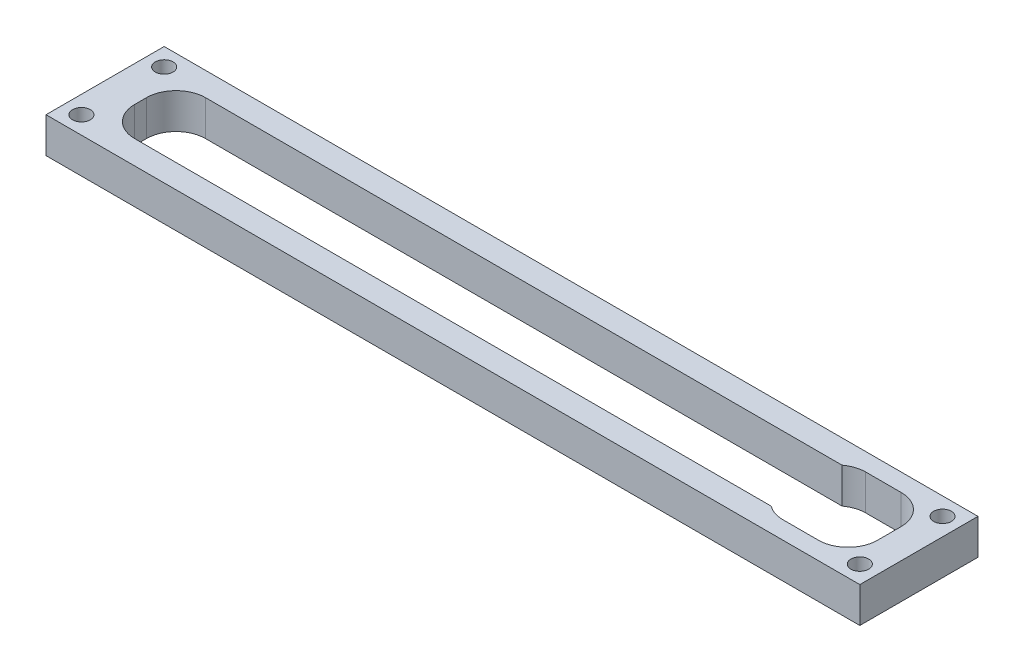
SolidWorks part; units mm, degrees
ref_plane "Front Plane" through (0, 0, 0) normal (0, 0, 1) x (1, 0, 0)
ref_plane "Top Plane" through (0, 0, 0) normal (0, 1, 0) x (1, 0, 0)
ref_plane "Right Plane" through (0, 0, 0) normal (1, 0, 0) x (0, 0, -1)
sketch "Sketch1" plane through (0, 0, 0) normal (0, 1, 0) x (1, 0, 0)
  line L0 (68.8639, 20) -> (68.8639, 0) construction
  line L1 (0, 0) -> (137.7278, 0)
  line L2 (0, 0) -> (0, 20)
  line L3 (0, 20) -> (137.7278, 20)
  line L4 (137.7278, 0) -> (137.7278, 20)
  line L5 (0, 10) -> (137.7278, 10) construction
  line L6 (68.8639, 16) -> (68.8639, 4) construction
  line L7 (6, 16) -> (131.7278, 16)
  line L8 (6, 16) -> (6, 4)
  line L9 (6, 4) -> (131.7278, 4)
  line L10 (131.7278, 16) -> (131.7278, 4)
  line L11 (6, 10) -> (131.7278, 10) construction
  circle A0 centre (3, 17) radius 1.5
  circle A1 centre (3, 3) radius 1.5
  circle A2 centre (134.7278, 3) radius 1.5
  circle A3 centre (134.7278, 17) radius 1.5
  point P17 (68.8639, 10)
  point P18 (68.8639, 10)
  dimension "D7" = 3
  dimension "D1" = 137.7278
  dimension "D2" = 20
  dimension "D3" = 125.7278
  dimension "D4" = 12
  dimension "D5" = 3
  dimension "D6" = 3
extrude "Boss-Extrude1" add sketch "Sketch1" along normal blind 6
sketch "Sketch2" plane through (0, 6, 0) normal (0, 1, 0) x (1, 0, 0)
  line L0 (92, 10) -> (-49908, 10) construction
  line L1 (131.7278, 4) -> (131.7278, 16) construction
  line L2 (118.7278, 17) -> (118.7278, 16)
  line L5 (131.7278, 16) -> (6, 16) construction
  line L6 (125.7278, 17) -> (125.7278, 3) construction
  line L7 (118.7278, 17) -> (132.7278, 17)
  line L9 (118.7278, 3) -> (132.7278, 3)
  line L10 (132.7278, 17) -> (132.7278, 3)
  line L12 (118.7278, 16) -> (131.7278, 16)
  line L13 (131.7278, 16) -> (131.7278, 4)
  line L14 (131.7278, 4) -> (118.7278, 4)
  line L15 (6, 4) -> (131.7278, 4) construction
  line L16 (118.7278, 4) -> (118.7278, 3)
  point P4 (131.7278, 10)
  point P23 (125.7278, 10)
  dimension "D1" = 1
  dimension "D2" = 14
  dimension "D3" = 14
extrude "Cut-Extrude1" cut sketch "Sketch2" against normal through all
fillet "Fillet1" radius 5 6 edges at (132.7278, 3, -17) (132.7278, 3, -3) (118.7278, 3, -17) (118.7278, 3, -3) (6, 3, -4) (6, 3, -16)
equation "\"TrackLength\"= ( ( \"n\" * 28 ) ) / cos ( \"MountAngle\" ) - ( 2 * \"x\" )"
equation "\"D1@Sketch1\"=\"TrackLength\""
equation "\"TrackWidth\"= \"MarbleTrackWidth\" + ( 2 * 4 )"
equation "\"D2@Sketch1\"=\"TrackWidth\""
equation "\"MarbleTrackWidth\"= \"MarbleWidth\" - 1"
equation "\"MarbleTrackLength\"= \"TrackLength\" - ( 2 * 6 )"
equation "\"D3@Sketch1\"=\"MarbleTrackLength\""
equation "\"D4@Sketch1\"=\"MarbleTrackWidth\""
equation "\"MarbleWidth\"= 13"
equation "\"n\"= 5"
equation "\"MountAngle\" = 10"
equation "\"x\"= 14 / cos ( \"MountAngle\" ) - 12"
